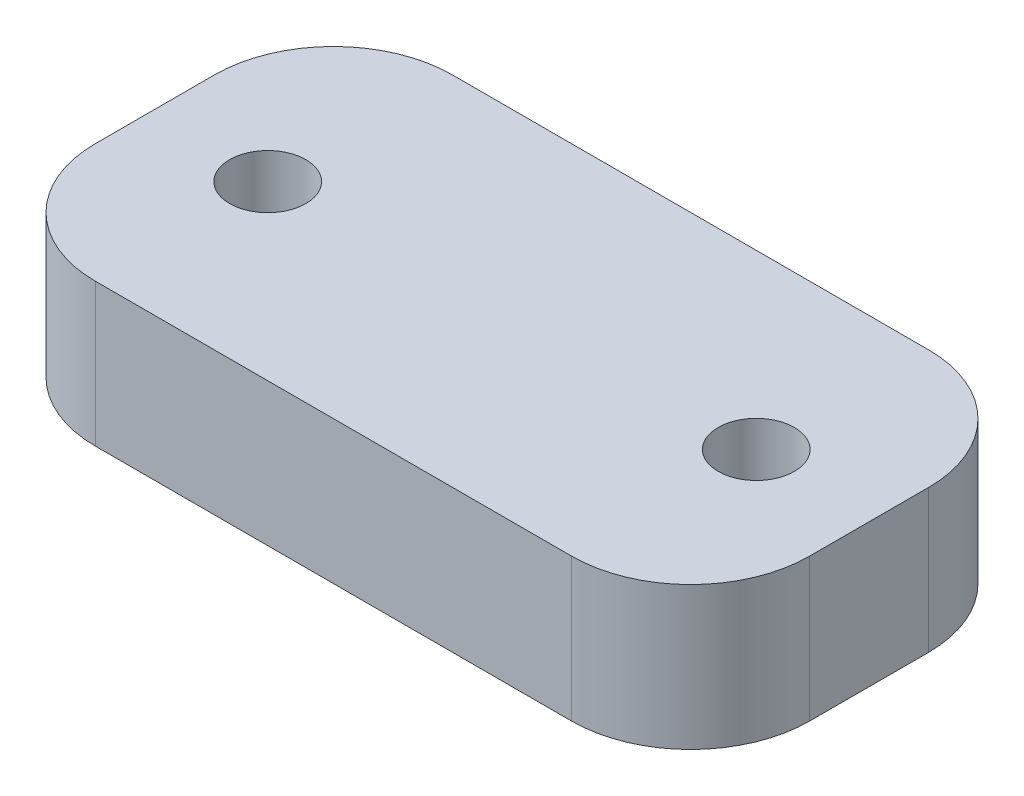
SolidWorks part; units mm, degrees
material "Maple"
ref_plane "Front Plane" through (0, 0, 0) normal (0, 0, 1) x (1, 0, 0)
ref_plane "Top Plane" through (0, 0, 0) normal (0, 1, 0) x (1, 0, 0)
ref_plane "Right Plane" through (0, 0, 0) normal (1, 0, 0) x (0, 0, -1)
sketch "Sketch1" plane through (0, 0, 0) normal (0, 1, 0) x (1, 0, 0)
  line L1 (-15, 7.5) -> (15, 7.5)
  line L2 (-15, 7.5) -> (-15, -7.5)
  line L3 (-15, -7.5) -> (15, -7.5)
  line L4 (15, 7.5) -> (15, -7.5)
  line L5 (-15, 7.5) -> (15, -7.5) construction
  line L6 (-15, -7.5) -> (15, 7.5) construction
  point P0 (0, 0)
  dimension "D1" = 30
  dimension "D2" = 15
extrude "Boss-Extrude1" add sketch "Sketch1" along normal blind 6
ref_plane "Plane1" through (0, 3, 0) normal (0, 1, 0) x (1, 0, 0)
hole_wizard "M3 Clearance Hole1" positions "Sketch3" profile "Sketch2" hole size "M3" standard "ANSI Metric" end condition through all
sketch "Sketch3" plane through (0, 6, 0) normal (0, 1, 0) x (1, 0, 0)
  line L0 (-10, -0.2591) -> (10, 0.2591) construction
  point P0 (-10, -0.2591)
  point P2 (10, 0.2591)
  dimension "D1" = 20
sketch "Sketch2" plane through (-10, 6, 0.2591) normal (1, 0, 0) x (0, 0, 1)
  line L0 (0, 0) -> (0, 6)
  line L1 (0, 6) -> (1.6, 6)
  line L2 (1.6, 6) -> (1.6, 0)
  line L5 (1.6, 0) -> (0, 0)
  line L11 (0, -6.35) -> (0, 107.95) construction
  dimension "Thru Hole Dia." = 3.2
  dimension "Thru Hole Depth" = 6
fillet "Fillet1" radius 5 4 edges at (15, 3, 7.5) (-15, 3, -7.5) (15, 3, -7.5) (-15, 3, 7.5)
